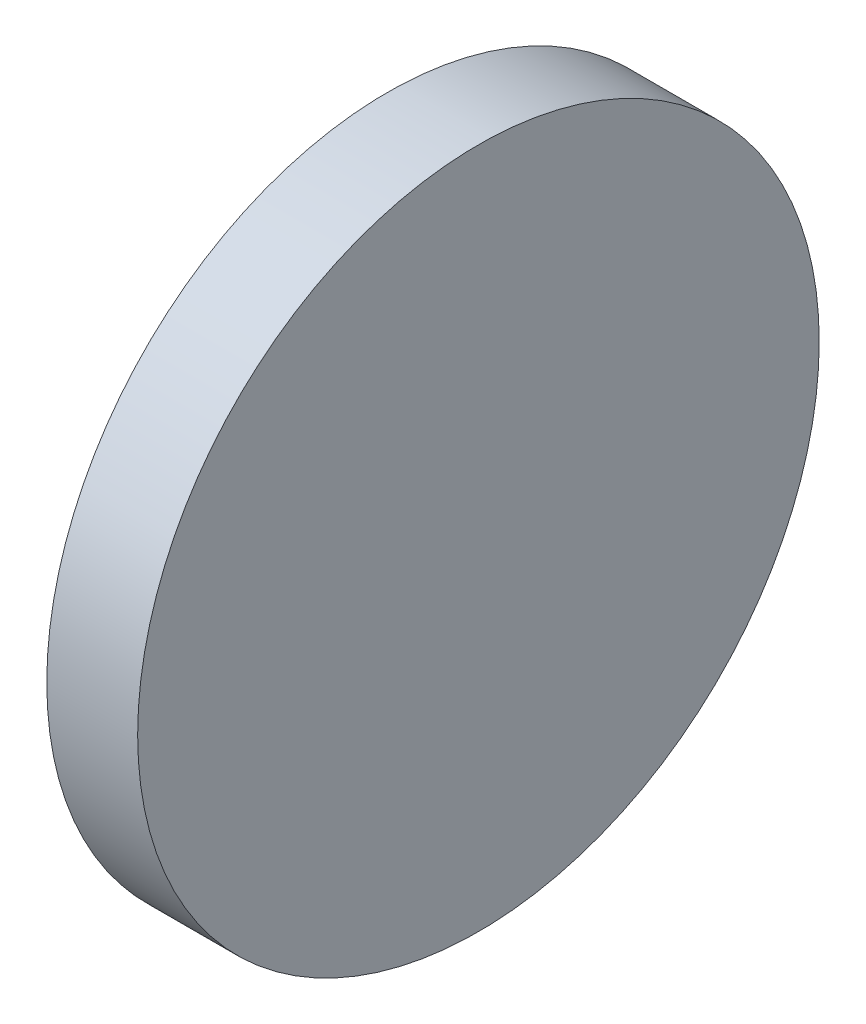
SolidWorks part; units mm, degrees
ref_plane "Спереди" through (0, 0, 0) normal (0, 0, 1) x (1, 0, 0)
ref_plane "Сверху" through (0, 0, 0) normal (0, 1, 0) x (1, 0, 0)
ref_plane "Справа" through (0, 0, 0) normal (1, 0, 0) x (0, 0, -1)
sketch "Эскиз1" plane through (0, 0, 0) normal (1, 0, 0) x (0, 0, -1)
  circle A0 centre (0, 0) radius 75
  dimension "D1" = 150
extrude "Бобышка-Вытянуть1" add sketch "Эскиз1" along normal blind 20
